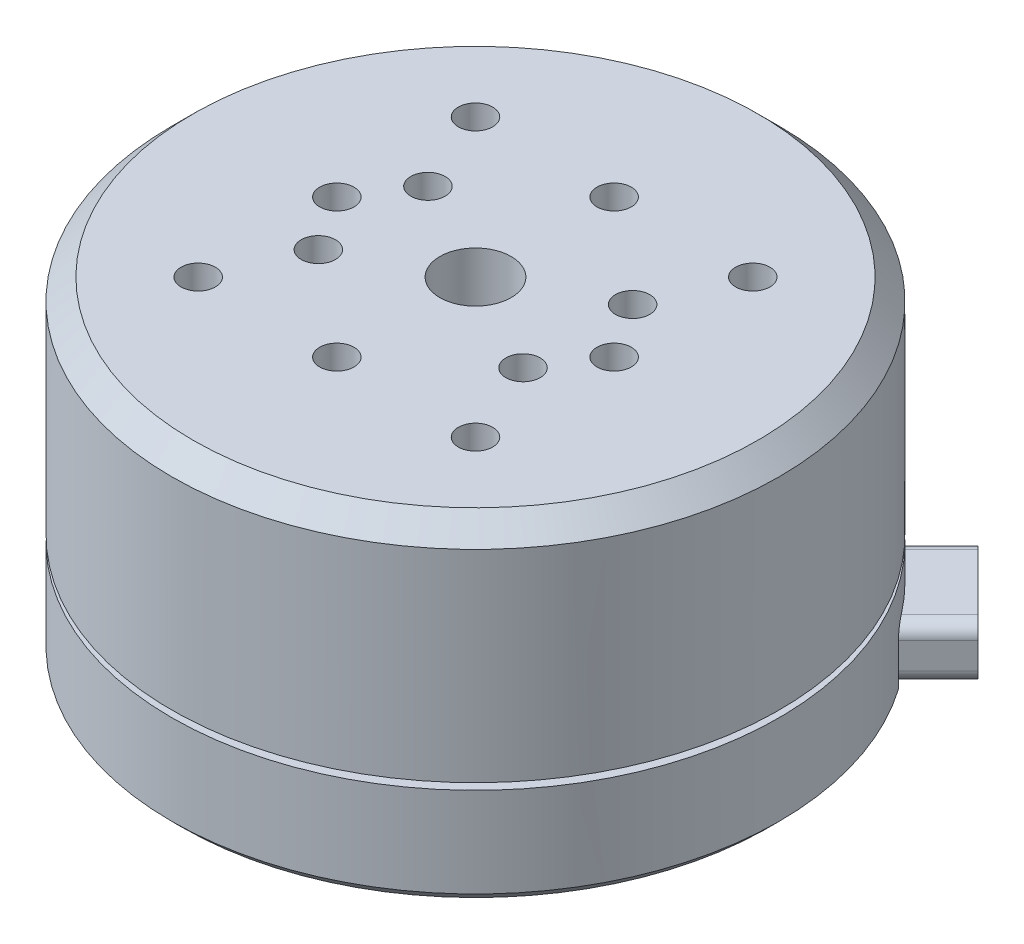
SolidWorks part; units mm, degrees
ref_plane "Front Plane" through (0, 0, 0) normal (0, 0, 1) x (1, 0, 0)
ref_plane "Top Plane" through (0, 0, 0) normal (0, 1, 0) x (1, 0, 0)
ref_plane "Right Plane" through (0, 0, 0) normal (1, 0, 0) x (0, 0, -1)
sketch "Sketch1" plane through (0, 0, 0) normal (0, 1, 0) x (1, 0, 0)
  circle A0 centre (0, 0) radius 23
  dimension "D1" = 46
extrude "Boss-Extrude1" add sketch "Sketch1" along normal blind 25
chamfer "Chamfer1" distance 1.6 angle 45 1 edges at (0, 25, 23)
chamfer "Chamfer2" distance 0.8 angle 45 1 edges at (0, 0, 23)
sketch "Sketch2" plane through (0, 0, 0) normal (0, -1, 0) x (1, 0, 0)
  circle A0 centre (0, 0) radius 6.5
  circle A1 centre (0, 0) radius 4.5
  dimension "D1" = 13
  dimension "D2" = 9
sketch "Sketch3" plane through (0, 0, 0) normal (0, -1, 0) x (1, 0, 0)
  line L0 (13.1872, -18.844) -> (18.844, -13.1872)
  line L1 (25.7965, 3.8457) -> (21.8078, 3.8457)
  line L2 (25.7965, 3.8457) -> (25.7965, -4.1543)
  line L3 (25.7965, -4.1543) -> (21.8078, -4.1543)
  line L4 (21.8078, 3.8457) -> (21.8078, -4.1543)
  line L5 (13.1872, -18.844) -> (16.1996, -21.8564)
  line L6 (18.844, -13.1872) -> (21.8564, -16.1996)
  line L7 (16.1996, -21.8564) -> (21.8564, -16.1996)
  circle A0 centre (0, 0) radius 22.2 construction
  circle A1 centre (0, 0) radius 23 construction
  dimension "D1" = 8
  dimension "D2" = 8
  dimension "D3" = 45
extrude "Boss-Extrude3" add sketch "Sketch3" against normal blind 5 contours L5 L7 L6 L0 region at (17.5218, 0, -17.5218)
extrude "Cut-Extrude2" cut sketch "Sketch3<2>" against normal blind 1 contours L5 L7 L6 L0 region at (17.5218, 0, -17.5218)
sketch "Sketch3<2>" plane through (0, 0, 0) normal (0, -1, 0) x (1, 0, 0) same geometry as "Sketch3"
fillet "Fillet1" radius 1 4 edges at (20.3502, 1, -14.6934) (14.6934, 1, -20.3502) (14.6934, 5, -20.3502) (20.3502, 5, -14.6934)
sketch "Sketch4" plane through (17.1277, 0, -20.9283) normal (-0.7071, 0, 0.7071) x (0.7071, 0, 0.7071)
  line L0 (-19.5125, 0) -> (24.8875, 0) construction
  line L1 (27.3273, 8.1) -> (-24.7552, 8.1)
  line L2 (27.3273, 8.1) -> (27.3273, 7.6)
  line L3 (27.3273, 7.6) -> (-24.7552, 7.6)
  line L4 (-24.7552, 8.1) -> (-24.7552, 7.6)
  dimension "D1" = 7.6
  dimension "D2" = 0.5
extrude "Cut-Extrude3" cut sketch "Sketch4" along normal blind 105
extrude "Boss-Extrude2" add sketch "Sketch2" along normal blind 0.1
sketch "Sketch5" plane through (0, 0, 0) normal (0, -1, 0) x (-1, 0, 0)
  line L0 (7.75, 7.75) -> (-7.75, -7.75)
  line L1 (-7.75, 7.75) -> (7.75, 7.75)
  line L2 (-7.75, 7.75) -> (-7.75, -7.75)
  line L3 (-7.75, -7.75) -> (7.75, -7.75)
  line L4 (7.75, 7.75) -> (7.75, -7.75)
  line L5 (-3.2102, -7.75) -> (7.75, 3.2102)
  line L6 (-3.2102, -7.75) -> (-7.75, -3.2102)
  line L7 (7.75, 3.2102) -> (3.2102, 7.75)
  line L8 (-7.75, -3.2102) -> (3.2102, 7.75)
  line L9 (-3.2102, -7.75) -> (3.2102, 7.75) construction
  line L10 (7.75, 3.2102) -> (-7.75, -3.2102) construction
  circle A0 centre (-7.75, 7.75) radius 1.3
  circle A1 centre (-7.75, -7.75) radius 1.3
  circle A2 centre (-7.75, -3.2102) radius 1.3
  circle A3 centre (-3.2102, -7.75) radius 1.3
  circle A4 centre (3.2102, 7.75) radius 1.3
  circle A5 centre (7.75, 7.75) radius 1.3
  circle A6 centre (7.75, 3.2102) radius 1.3
  circle A7 centre (7.75, -7.75) radius 1.3
  point P7 (0, 0)
  dimension "D1" = 15.5
  dimension "D3" = 7.75
  dimension "D4" = 7.75
  dimension "D2" = 15.5
  dimension "D5" = 15.5
  dimension "D6" = 0
  dimension "D7" = 0
sketch "Sketch6" plane through (0, 25, 0) normal (0, 1, 0) x (1, 0, 0)
  line L1 (-10.5, 10.5) -> (10.5, 10.5)
  line L2 (-10.5, 10.5) -> (-10.5, -10.5)
  line L3 (-10.5, -10.5) -> (10.5, -10.5)
  line L4 (10.5, 10.5) -> (10.5, -10.5)
  line L5 (-7.75, 4.15) -> (7.75, 4.15)
  line L6 (-7.75, 4.15) -> (-7.75, -4.15)
  line L7 (-7.75, -4.15) -> (7.75, -4.15)
  line L8 (7.75, 4.15) -> (7.75, -4.15)
  circle A0 centre (-10.5, 10.5) radius 1.3
  circle A1 centre (0, 10.5) radius 1.3
  circle A2 centre (10.5, 10.5) radius 1.3
  circle A3 centre (-10.5, 0) radius 1.3
  circle A4 centre (-10.5, -10.5) radius 1.3
  circle A5 centre (10.5, -10.5) radius 1.3
  circle A6 centre (0, -10.5) radius 1.3
  circle A7 centre (10.5, 0) radius 1.3
  circle A8 centre (7.75, 4.15) radius 1.3
  circle A9 centre (-7.75, 4.15) radius 1.3
  circle A10 centre (-7.75, -4.15) radius 1.3
  circle A11 centre (7.75, -4.15) radius 1.3
  dimension "D1" = 21
  dimension "D3" = 10.5
  dimension "D4" = 10.5
  dimension "D2" = 21
  dimension "D5" = 15.5
  dimension "D6" = 8.3
  dimension "D7" = 7.75
  dimension "D8" = 4.15
extrude "Cut-Extrude5" cut sketch "Sketch6" against normal blind 4 contours A0 | A1 | A2 | A8 | A7 | A11 | A5 | A6 | A4 | A10 | A3 | A9
extrude "Cut-Extrude6" cut sketch "Sketch5" against normal blind 4 contours A0 | A4 | A5 | A6 | A7 | A3 | A1 | A2
sketch "Sketch7" plane through (0, 0, 0) normal (0, -1, 0) x (1, 0, 0)
  circle A0 centre (0, 0) radius 4.5
  circle A1 centre (0, 0) radius 2.7
  dimension "D1" = 5.4
  dimension "D2" = 9
extrude "Boss-Extrude4" add sketch "Sketch7" along normal blind 0.6 and the other way blind 10
chamfer "Chamfer3" distance 0.5 angle 45 1 edges at (0, -0.6, -4.5)
extrude "Cut-Extrude8" cut sketch "Sketch7<3>" against normal blind 66.6 contours A1 region at (0, 0, 0)
sketch "Sketch7<3>" plane through (0, 0, 0) normal (0, -1, 0) x (1, 0, 0) same geometry as "Sketch7"
